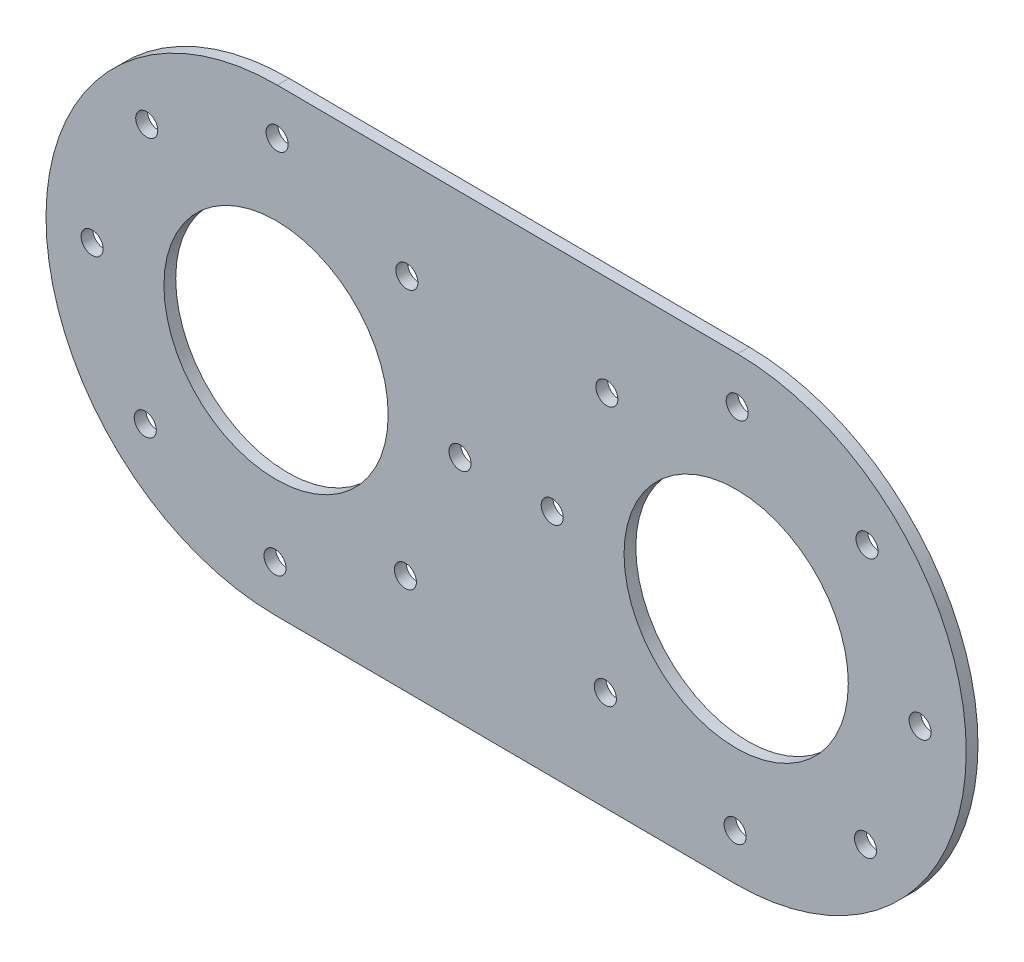
SolidWorks part; units mm, degrees
ref_plane "Front Plane" through (0, 0, 0) normal (0, 0, 1) x (1, 0, 0)
ref_plane "Top Plane" through (0, 0, 0) normal (0, 1, 0) x (1, 0, 0)
ref_plane "Right Plane" through (0, 0, 0) normal (1, 0, 0) x (0, 0, -1)
sketch "Sketch1" plane through (0, 0, 0) normal (0, 0, 1) x (1, 0, 0)
  line L0 (46.9003, -3.7607) -> (-15.6334, -3.4065)
  line L1 (0.0885, 12.1384) -> (31.3554, 11.9613)
  line L2 (-0.0885, -19.1285) -> (31.1784, -19.3056)
  circle A0 centre (31.2669, -3.6722) radius 15.6337 construction
  circle A1 centre (0, -3.4951) radius 15.6337
  circle A2 centre (0, -3.4951) radius 15.6337
  circle A3 centre (31.2669, -3.6722) radius 15.6337
  circle A6 centre (-12.5, -3.4243) radius 0.75
  circle A7 centre (-8.7888, 5.3938) radius 0.75
  circle A8 centre (0.0708, 9.0049) radius 0.75
  circle A9 centre (8.8889, 5.2937) radius 0.75
  circle A10 centre (12.5, -3.5659) radius 0.75
  circle A11 centre (8.7888, -12.384) radius 0.75
  circle A12 centre (-0.0708, -15.9951) radius 0.75
  circle A13 centre (-8.8889, -12.2838) radius 0.75
  circle A14 centre (43.7669, -3.743) radius 0.75
  circle A16 centre (40.0557, -12.5611) radius 0.75
  circle A17 centre (31.1961, -16.1722) radius 0.75
  circle A18 centre (22.378, -12.4609) radius 0.75
  circle A19 centre (18.7669, -3.6014) radius 0.75
  circle A20 centre (22.4781, 5.2167) radius 0.75
  circle A21 centre (31.3377, 8.8278) radius 0.75
  circle A22 centre (40.1558, 5.1166) radius 0.75
  circle A23 centre (0, -3.4951) radius 7.62
  circle A24 centre (31.2669, -3.6722) radius 7.62
  point P7 (31.2669, -3.6722)
  point P8 (0, -3.4951)
  point P28 (0, -3.4951)
  point P46 (31.2669, -3.6722)
  dimension "D2" = 12.5
  dimension "D4" = 12.5
  dimension "D5" = 1.5
  dimension "D6" = 1.5
  dimension "D8" = 15.24
  dimension "D9" = 15.24
  dimension "D1" = 0
  dimension "D3" = 8
  dimension "D7" = 8
extrude "Boss-Extrude1" add sketch "Sketch1" along normal blind 0.8 contours A19 L0 A3 A14 A18 A17 A16 | A19 L0 A14 A3 A22 A21 A20 | A10 L0 A2 A6 A9 A8 A7 | A10 L0 A6 A2 A13 A12 A11 | A3 L1 A2 | A3 A2 L2 region at (31.2233, -11.3687, 0) region at (31.3105, 4.0244, 0) region at (15.5647, -15.7251, 0) region at (-0.0436, -11.1916, 0) region at (0.0436, 4.2015, 0) region at (15.7022, 8.5578, 0)
